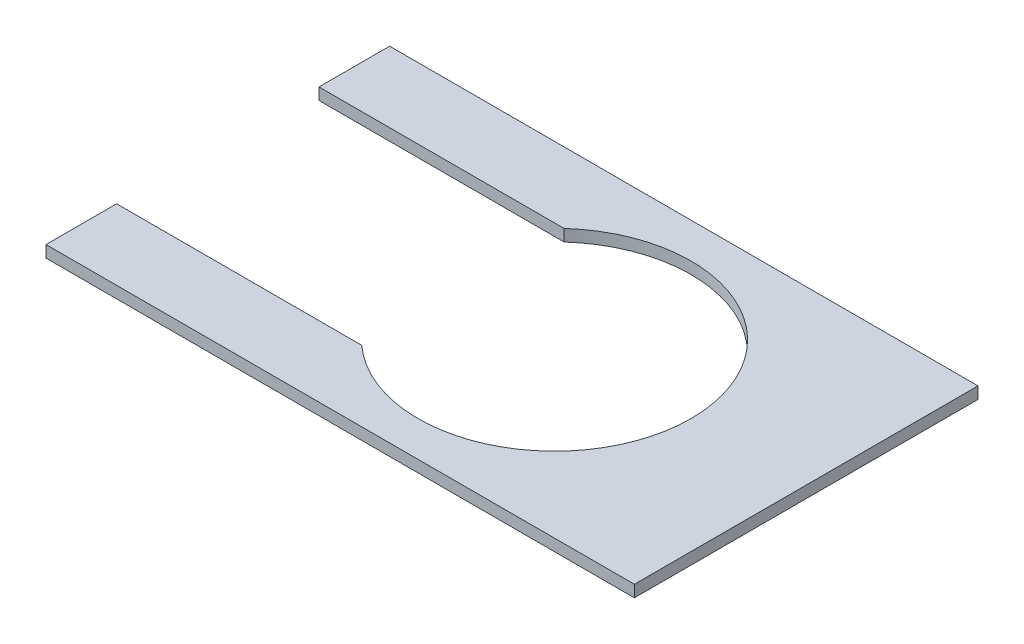
SolidWorks part; units mm, degrees
ref_plane "Front Plane" through (0, 0, 0) normal (0, 0, 1) x (1, 0, 0)
ref_plane "Top Plane" through (0, 0, 0) normal (0, 1, 0) x (1, 0, 0)
ref_plane "Right Plane" through (0, 0, 0) normal (1, 0, 0) x (0, 0, -1)
sketch "Sketch1" plane through (0, 0, 0) normal (0, 1, 0) x (1, 0, 0)
  line L0 (-118.6638, 10) -> (-118.6638, -20) construction
  line L5 (-228.6638, 10) -> (-118.6638, 10)
  line L6 (-228.6638, 10) -> (-228.6638, -20)
  line L7 (-228.6638, -20) -> (-124.5174, -20)
  line L11 (-118.6638, 10) -> (21.3362, 10)
  line L12 (21.3362, -106) -> (21.3362, 10)
  line L13 (-118.6638, -20) -> (-118.6638, -106) construction
  line L14 (-118.6638, -63) -> (-88.6227, -63) construction
  line L24 (-183.6227, -20) -> (-183.6227, -106) construction
  line L26 (21.3362, -106) -> (21.3362, -136)
  line L28 (-118.6638, -136) -> (21.3362, -136)
  line L29 (-228.6638, -136) -> (-118.6638, -136)
  line L30 (-228.6638, -136) -> (-228.6638, -106)
  line L31 (-228.6638, -106) -> (-124.5174, -106)
  line L34 (-73.6638, -20) -> (-73.6638, -106) construction
  arc A2 (-158.108, -20) -> (-209.1375, -20) centre (-183.6227, -63) ccw construction
  arc A6 (-124.5174, -106) -> (-124.5174, -20) centre (-85.5944, -63) ccw
  circle A7 centre (-183.6227, -63) radius 43 construction
  point P24 (-183.6227, -63)
  dimension "D7" = 116
  dimension "D1" = 110
  dimension "D2" = 30
  dimension "D3" = 86
  dimension "D5" = 140
extrude "Boss-Extrude1" add sketch "Sketch1" along normal blind 5
